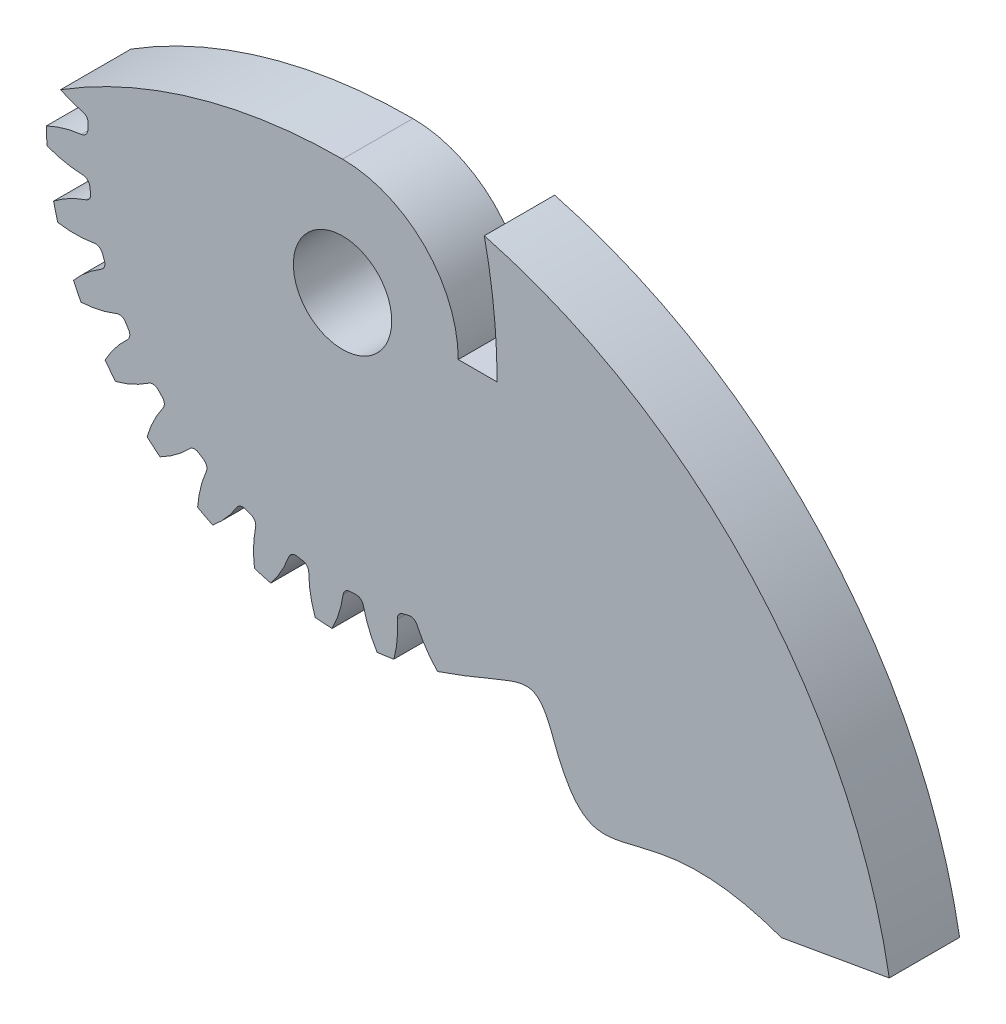
SolidWorks part; units mm, degrees
material "ABS"
ref_plane "Front" through (0, 0, 0) normal (0, 0, 1) x (1, 0, 0)
ref_plane "Top" through (0, 0, 0) normal (0, 1, 0) x (1, 0, 0)
ref_plane "Right" through (0, 0, 0) normal (1, 0, 0) x (0, 0, -1)
sketch "Sketch3" plane through (0, 0, 0) normal (0, 0, 1) x (1, 0, 0)
  circle A0 centre (0, 0) radius 40.64
  dimension "od" = 81.28
extrude "gearBody" add sketch "Sketch3" along normal blind 9.652
sketch "Sketch2" plane through (0, 0, 0) normal (0, 0, 1) x (1, 0, 0)
  line L0 (0, 0) -> (34.0786, 14.1158) construction
  line L1 (45.4751, -11.4855) -> (0, 0) construction
  line L2 (0, 0) -> (36.3143, 0) construction
  line L3 (38.0972, -0.458) -> (37.8451, -4.4001) construction
  line L5 (37.9712, -2.4291) -> (0, 0) construction
  line L7 (0, 0) -> (36.8864, 0) construction
  arc A0 (36.879, -0.7403) -> (36.6727, -3.9649) centre (0, 0) ccw construction
  arc A1 (40.637, 0.4947) -> (40.2427, -5.6687) centre (0, 0) ccw construction
  arc A2 (38.0972, -0.458) -> (37.8451, -4.4001) centre (0, 0) ccw construction
  arc A3 (34.9015, -2.6404) -> (34.9534, -1.8283) centre (0, 0) ccw
  arc A4 (45.4751, -11.4855) -> (35.6466, -3.6712) centre (32.0022, -18.3431) ccw
  arc A5 (45.4751, -11.4855) -> (46.5679, 5.5974) centre (0, 0) ccw
  arc A6 (46.5679, 5.5974) -> (35.8238, -0.9008) centre (34.0786, 14.1158) cw
  arc A7 (34.9534, -1.8283) -> (35.8238, -0.9008) centre (35.9376, -1.8798) cw
  arc A8 (35.6466, -3.6712) -> (34.9015, -2.6404) centre (35.8842, -2.7147) cw
  point P6 (46.5679, 5.5974)
  point P22 (45.4751, -11.4855)
  dimension "baseDia" = 73.7729
  dimension "od" = 81.28
  dimension "pd" = 76.2
  dimension "rd" = 70.0024
  dimension "rFillet" = 0.9855
  dimension "pointX" = 46.5679
  dimension "pointY" = 5.5974
  dimension "CTT" = 3.9421
  dimension "flankCenterAngle" = 22.5
extrude "toothCut" cut sketch "Sketch2" along normal through all
pattern_circular "CirPattern1" count 30 over 360 about axis through (0, 0, 9.652) along (0, 0, -1) of "toothCut"
sketch "hub1Dia" plane through (0, 0, 0) normal (0, 0, -1) x (-1, 0, 0)
  circle A0 centre (0, 0) radius 12.7
  dimension "hub1Dia" = 25.4
sketch "hub2Dia" plane through (0, 0, 9.652) normal (0, 0, 1) x (1, 0, 0)
  circle A0 centre (0, 0) radius 12.7
  dimension "hub2dia" = 25.4
sketch "boreDia" plane through (0, 0, 0) normal (0, 0, 1) x (1, 0, 0)
  circle A0 centre (0, 0) radius 6.7469
  dimension "boreDia" = 13.4937
extrude "bore" cut sketch "boreDia" against normal mid plane 25400
sketch "Sketch4" plane through (0, 0, 9.652) normal (0, 0, 1) x (1, 0, 0)
  circle A0 centre (0, -57.15) radius 76.1746
  arc A2 (-41.7195, 6.5842) -> (41.7195, 6.5842) centre (0, 0) cw
  dimension "D1" = 152.3492
  dimension "D2" = 57.15
extrude "Cut-Extrude1" cut sketch "Sketch4" against normal through all contours A0 region at (0, 26.0638, 9.652)
sketch "Sketch5" plane through (0, 0, 9.652) normal (0, 0, 1) x (1, 0, 0)
  line L0 (0, 19.0246) -> (21.5163, 3.7176)
  line L1 (21.5163, 3.7176) -> (8.9608, -26.928)
  line L2 (8.9608, -26.928) -> (13.028, -38.4952)
  line L3 (0, 0) -> (0, -57.15) construction
  line L4 (0, -57.15) -> (-54.1615, -3.586) construction
  line L5 (0, -57.15) -> (65.9691, -95.2373) construction
  line L9 (0, -57.15) -> (75.0173, -43.9224) construction
  line L12 (60.232, -46.5295) -> (75.0173, -43.9224)
  line L13 (0, -57.15) -> (29.696, -40.005) construction
  line L14 (29.696, -40.005) -> (26.521, -34.5057) construction
  circle A1 centre (0, -57.15) radius 76.1746 construction
  arc A5 (0, 19.0246) -> (75.0173, -43.9224) centre (0, -57.15) cw
  circle A6 centre (0, -57.15) radius 21.59 construction
  circle A12 centre (49.4934, -85.725) radius 40.64 construction
  spline S0 degree 3 poles (13.028, -38.4952) (20.557, -35.948) (26.6517, -31.726) (34.6651, -56.7545) (39.5345, -39.0169) (60.232, -46.5295) knots 0 0 0 0 0.118515 0.218515 1 1 1 1
  point P28 (21.569, -56.1981)
  dimension "D1" = 43.18
  dimension "D3" = 81.28
  dimension "D6" = 152.3492
  dimension "D2" = 120
  dimension "D4" = 57.15
  dimension "D8" = 57.15
  dimension "D7" = 60
  dimension "D9" = 34.29
  dimension "D10" = 6.35
  dimension "D5" = 80
extrude "Boss-Extrude1" add sketch "Sketch5" against normal up to surface (9.652 mm away) up to face at (6.7469, 0, 0)
sketch "Sketch6" plane through (0, 0, 9.652) normal (0, 0, 1) x (1, 0, 0)
  line L1 (-41.2993, 3.0747) -> (-42.3397, 6.1739)
  line L2 (15.875, 0) -> (21.209, 0)
  circle A0 centre (0, -57.15) radius 76.1746 construction
  arc A1 (75.0173, -43.9224) -> (-34.0662, 10.9827) centre (0, -57.15) ccw construction
  circle A2 centre (0, 0) radius 15.875 construction
  arc A3 (0, 15.875) -> (15.875, 0) centre (0, 0) cw
  arc A4 (19.4523, 16.499) -> (-42.3397, 6.1739) centre (0, -57.15) ccw
  arc A5 (0, 15.875) -> (-41.2993, 3.0747) centre (0, -57.15) ccw
  circle A6 centre (0, 0) radius 21.209 construction
  circle A8 centre (-57.15, 0) radius 78.359 construction
  arc A9 (21.209, 0) -> (19.4523, 16.499) centre (-57.15, 0) ccw
  dimension "D4" = 57.15
  dimension "D1" = 31.75
  dimension "D2" = 42.418
  dimension "D3" = 156.718
extrude "Cut-Extrude2" cut sketch "Sketch6" against normal through all
equation "\"Bodytube_OD\" = 6.17in"
equation "\"Bodytube_ID\" = 5.998in"
equation "\"Fwd_Tube_Length\" = 40in"
equation "\"Mid_Tube_Length\" = 1in"
equation "\"Aft_Section_Length\"= 39in"
equation "\"Mid_Coupler_Length\"= 13in"
equation "\"Aft_Lower_Length\"= 22in"
equation "\"AB_Coupler_OD_Length\"= 1in"
equation "\"AB_Coupling_Section_Length\"= 0.375in"
equation "\"AB_Coupler_Length\"= \"AB_Coupler_OD_Length\" + \"AB_Coupling_Section_Length\" * 2"
equation "\"Cutout_Angle\" = 80"
equation "\"AB_Paddle_Height\" = 0.375in"
equation "\"AB_Coupler_Num_Screws\"= 4"
equation "\"Num_Cutouts\" = 3"
equation "\"AB_Coupler_OD\"= 6.17in"
equation "\"AB_Coupler_ID\"= 5.75in"
equation "\"AB_Coupler_Surface_Diameter\"= 5.998in"
equation "\"AB_Coupling_Screw_Diameter\"= 0.15748in"
equation "\"AB_Central_Bushing_Length\" = .4724in"
equation "\"Lead_Screw_Dist\" = 3.4in"
equation "\"Lead_Screw_Diam\" = 0.386in"
equation "\"Lead_Screw_Length\" = (\"Mid_Coupler_Length\" + 2*0.375in + 2*0.5in)"
equation "\"Paddle_Pin_Offset\" = .25in"
equation "\"Paddle_Pin_Radius\" = 2.25in"
equation "\"Fwd_BKHD_From_Top\" = 18in"
equation "\"D1@Sketch4\"=\"Bodytube_ID\""
equation "\"D2@Sketch4\"=\"Paddle_Pin_Radius\""
equation "\"D3@Sketch5\"=\"Paddle_Gear_OD\""
equation "\"D4@Sketch5\"=\"Paddle_Pin_Radius\""
equation "\"Motor_OD\" = 4in"
equation "\"Aft_Upper_Length\"= \"Aft_Section_Length\" - \"Aft_Lower_Length\" - \"AB_Coupler_OD_Length\""
equation "\"Paddle_Gear_OD\" = 3.2in"
equation "\"D5@Sketch5\"=\"Cutout_Angle\""
equation "\"D6@Sketch5\"=\"Bodytube_ID\""
equation "\"D1@Sketch6\"=\"AB_Coupler_ID\"-2*\"Paddle_Pin_Radius\""
equation "\"D2@Sketch6\"=\"Bodytube_OD\"-2*\"Paddle_Pin_Radius\""
equation "\"D3@Sketch6\"=\"Bodytube_OD\""
equation "\"D4@Sketch6\"=\"Paddle_Pin_Radius\""
equation "\"D8@Sketch5\"=\"Paddle_Pin_Radius\""
equation "\"Drive_Gear_OD\" = 1.7in"
equation "\"Fin_Thickness\"= .118in"
equation "\"Guiderail_Cutout_Diameter\"= 1.5in"
equation "\"DB9_Hole_Dist\" = 25mm"
equation "\"D1@Sketch5\"=\"Drive_Gear_OD\""
